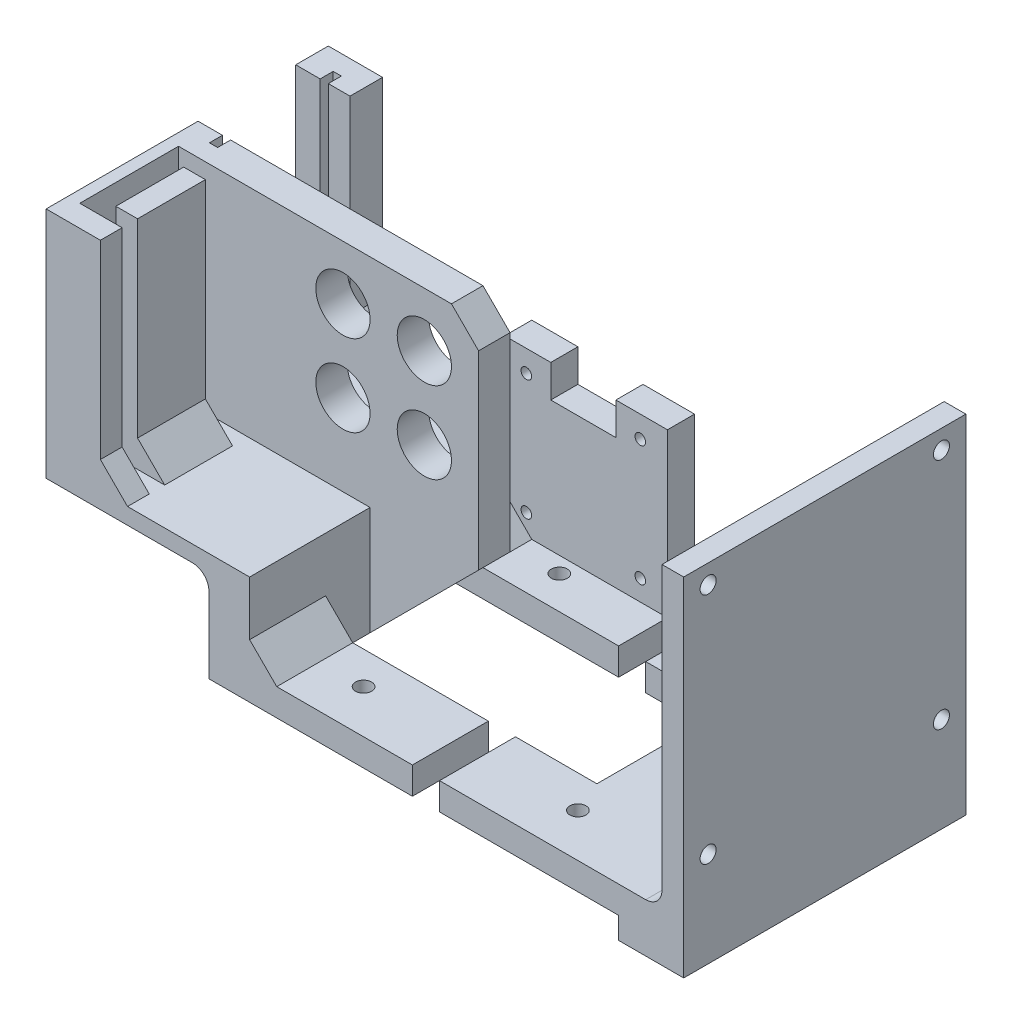
SolidWorks part; units mm, degrees
note: The reader was unsure of these and kept them because the rebuilt part matched: shared geometry of "草图12<4>".
ref_plane "前视基准面" through (0, 0, 0) normal (0, 0, 1) x (1, 0, 0)
ref_plane "上视基准面" through (0, 0, 0) normal (0, 1, 0) x (1, 0, 0)
ref_plane "右视基准面" through (0, 0, 0) normal (1, 0, 0) x (0, 0, -1)
sketch "草图1" plane through (0, 0, 0) normal (0, 1, 0) x (1, 0, 0)
  line L1 (-43.75, 31) -> (43.75, 31)
  line L2 (-43.75, 31) -> (-43.75, -31)
  line L3 (-43.75, -31) -> (43.75, -31)
  line L4 (43.75, 31) -> (43.75, -31)
  line L5 (-43.75, 31) -> (43.75, -31) construction
  line L6 (-43.75, -31) -> (43.75, 31) construction
  point P0 (0, 0)
  dimension "D1" = 62
  dimension "D2" = 87.5
extrude "凸台-拉伸1" add sketch "草图1" along normal blind 60
sketch "草图2" plane through (0, 0, 0) normal (0, -1, 0) x (1, 0, 0)
  line L0 (43.75, -31) -> (-43.75, -31) construction
  line L1 (43.75, 31) -> (31.75, 31)
  line L2 (43.75, 31) -> (43.75, -31)
  line L3 (43.75, -31) -> (31.75, -31)
  line L4 (31.75, 31) -> (31.75, -31)
  dimension "D1" = 12
extrude "凸台-拉伸2" add sketch "草图2" along normal blind 4
sketch "草图4" plane through (0, 0, 0) normal (0, -1, 0) x (1, 0, 0)
  line L0 (0, 0) -> (43.75, 0) construction
  line L1 (43.75, -31) -> (43.75, 31) construction
  line L2 (31.75, 31) -> (31.75, -31) construction
  line L3 (19.75, 6) -> (29.75, 6)
  line L4 (19.75, 6) -> (19.75, -6)
  line L5 (19.75, -6) -> (29.75, -6)
  line L6 (29.75, 6) -> (29.75, -6)
  line L7 (19.75, 6) -> (29.75, -6) construction
  line L8 (19.75, -6) -> (29.75, 6) construction
  line L9 (0, 0) -> (-43.75, 0) construction
  line L10 (-43.75, -31) -> (-43.75, 31) construction
  line L12 (-36.25, 12) -> (13.75, 12)
  line L13 (-36.25, 12) -> (-36.25, -12)
  line L14 (-36.25, -12) -> (13.75, -12)
  line L15 (13.75, 12) -> (13.75, -12)
  line L16 (-36.25, 12) -> (13.75, -12) construction
  line L17 (-36.25, -12) -> (13.75, 12) construction
  circle A0 centre (16.25, -18) radius 1.48 construction
  circle A3 centre (16.25, -18) radius 1.48
  circle A4 centre (-23.25, 18) radius 1.48 construction
  circle A5 centre (-23.25, -18.0759) radius 1.48 construction
  circle A6 centre (-23.25, -18.0759) radius 1.48
  circle A7 centre (-23.25, 18) radius 1.48
  circle A8 centre (16.25, 18) radius 1.48 construction
  circle A9 centre (16.25, 18) radius 1.48
  point P17 (24.75, 0)
  point P27 (-11.25, 0)
  dimension "D1" = 2
  dimension "D2" = 10
  dimension "D3" = 12
  dimension "D4" = 24
  dimension "D5" = 50
  dimension "D6" = 6
extrude "切除-拉伸2" cut sketch "草图4" against normal blind 10
sketch "草图6" plane through (0, 60, 0) normal (0, 1, 0) x (1, 0, 0)
  line L0 (-43.75, 31) -> (-43.75, -31) construction
  line L1 (43.75, -31) -> (-43.75, -31)
  line L2 (43.75, -31) -> (43.75, -26)
  line L3 (43.75, -26) -> (-43.75, -26)
  line L4 (-43.75, -31) -> (-43.75, -26)
  line L5 (40.679, 0) -> (-87.179, 0) construction
  line L6 (43.75, 26) -> (-43.75, 26)
  line L7 (-43.75, 31) -> (-43.75, 26)
  line L8 (43.75, 31) -> (-43.75, 31)
  line L9 (43.75, 31) -> (43.75, 26)
  dimension "D1" = 5
extrude "切除-拉伸3" cut sketch "草图6" against normal blind 100
sketch "草图7" plane through (-43.75, 0, 0) normal (-1, 0, 0) x (0, 0, 1)
  line L0 (26, 0) -> (26, 60) construction
  line L1 (-26, 60) -> (26, 60)
  line L2 (-26, 60) -> (-26, 17)
  line L3 (-26, 17) -> (26, 17)
  line L4 (26, 60) -> (26, 17)
  dimension "D1" = 43
extrude "凸台-拉伸3" add sketch "草图7" along normal blind 30
sketch "草图9" plane through (0, 60, 0) normal (0, 1, 0) x (1, 0, 0)
  line L0 (0, 0) -> (-63.75, 0) construction
  line L1 (39.75, -26) -> (-63.75, -26)
  line L2 (39.75, -26) -> (39.75, 26)
  line L3 (39.75, 26) -> (-63.75, 26)
  line L4 (-73.75, -26) -> (43.75, -26)
  line L5 (43.75, -26) -> (43.75, 26)
  line L6 (43.75, 26) -> (-73.75, 26)
  line L7 (-73.75, 26) -> (-73.75, -26)
  line L8 (-73.75, -26) -> (43.75, -26)
  line L9 (43.75, -26) -> (43.75, 26)
  line L10 (43.75, 26) -> (-73.75, 26)
  line L11 (-73.75, 26) -> (-73.75, -26)
  line L12 (-63.75, -26) -> (-63.75, 26)
  dimension "D2" = 4
  dimension "D3" = 10
  dimension "D1" = 0
extrude "切除-拉伸4" cut sketch "草图9" against normal blind 40 contours L2 L1 L12 L3
sketch "草图10" plane through (0, 20, 0) normal (0, 1, 0) x (1, 0, 0)
  line L1 (39.75, -26) -> (-36.25, -26)
  line L2 (39.75, -26) -> (39.75, 26)
  line L3 (39.75, 26) -> (-36.25, 26)
  line L4 (39.75, 26) -> (-63.75, 26)
  line L5 (-63.75, 26) -> (-63.75, -26)
  line L6 (-63.75, -26) -> (39.75, -26)
  line L7 (39.75, -26) -> (39.75, 26)
  line L8 (39.75, 26) -> (-63.75, 26)
  line L9 (-63.75, 26) -> (-63.75, -26)
  line L10 (-63.75, -26) -> (39.75, -26)
  line L11 (39.75, -26) -> (39.75, 26)
  line L12 (-36.25, -26) -> (-36.25, 26)
  line M7 (39.75, 26) -> (-63.75, 26)
  line M9 (-63.75, -26) -> (39.75, -26)
  line M10 (39.75, -26) -> (39.75, 26)
  dimension "D2" = 76
  dimension "D1" = 0
extrude "切除-拉伸5" cut sketch "草图10" against normal blind 15 contours L12 M9 M10 M7
sketch "草图11" plane through (43.75, 0, 0) normal (1, 0, 0) x (0, 0, -1)
  line L0 (0, 0) -> (0, 60) construction
  line L1 (-26, 60) -> (26, 60) construction
  line L3 (-21.5, 56.5) -> (21.5, 56.5) construction
  line L4 (-21.5, 56.5) -> (-21.5, 13.5) construction
  line L5 (-21.5, 13.5) -> (21.5, 13.5) construction
  line L6 (21.5, 56.5) -> (21.5, 13.5) construction
  line L7 (-21.5, 56.5) -> (21.5, 13.5) construction
  line L8 (-21.5, 13.5) -> (21.5, 56.5) construction
  circle A0 centre (-21.5, 56.5) radius 1.48
  circle A1 centre (21.5, 56.5) radius 1.48
  circle A2 centre (-21.5, 13.5) radius 1.48
  circle A3 centre (21.5, 13.5) radius 1.48
  point P5 (0, 35)
  dimension "D1" = 43
  dimension "D2" = 43
  dimension "D3" = 25
extrude "切除-拉伸6" cut sketch "草图11" against normal blind 10
sketch "草图12" plane through (0, 60, 0) normal (0, 1, 0) x (1, 0, 0)
  line L0 (-63.75, -26) -> (-63.75, 26) construction
  line L1 (-63.75, -19.15) -> (-67.75, -19.15)
  line L2 (-63.75, -19.15) -> (-63.75, -6.65)
  line L3 (-63.75, -6.65) -> (-67.75, -6.65)
  line L4 (-67.75, -19.15) -> (-67.75, -6.65)
  line L5 (-63.75, -26) -> (-73.75, -26) construction
  line L6 (-63.75, -3.8) -> (-71.55, -3.8)
  line L7 (-63.75, -3.8) -> (-63.75, -22)
  line L8 (-63.75, -22) -> (-71.55, -22)
  line L9 (-71.55, -3.8) -> (-71.55, -22)
  line L10 (-73.75, 26) -> (-63.75, 26) construction
  line L11 (-63.75, 20) -> (-67.75, 20)
  line L12 (-63.75, 20) -> (-63.75, 2)
  line L13 (-63.75, 2) -> (-67.75, 2)
  line L14 (-67.75, 20) -> (-67.75, 2)
  line L15 (-73.75, -26) -> (-73.75, 26) construction
  line L16 (-67.75, 22.4) -> (-69.25, 22.4)
  line L17 (-67.75, 22.4) -> (-67.75, -0.4)
  line L18 (-67.75, -0.4) -> (-69.25, -0.4)
  line L19 (-69.25, 22.4) -> (-69.25, -0.4)
  line L20 (-69.25, 20) -> (-73.75, 20)
  line L21 (-69.25, 20) -> (-69.25, 2)
  line L22 (-69.25, 2) -> (-73.75, 2)
  line L23 (-73.75, 20) -> (-73.75, 2)
  line M6 (-63.75, -26) -> (-63.75, 26)
  line M8 (-73.75, 26) -> (-73.75, -26)
  dimension "D1" = 12.5
  dimension "D2" = 4
  dimension "D3" = 18.2
  dimension "D4" = 2.85
  dimension "D5" = 4
  dimension "D6" = 3.8
  dimension "D7" = 4
  dimension "D8" = 18
  dimension "D9" = 6
  dimension "D10" = 1.5
  dimension "D11" = 22.8
  dimension "D12" = 2.4
extrude "切除-拉伸7" cut sketch "草图12" against normal blind 40 contours L6 L9 L8 L1 L4 L3 M6
extrude "切除-拉伸8" cut sketch "草图12<4>" against normal blind 40 contours L16 L19 L18 L17 L14 | L11 L14 L13 M6 | L22 L19 L20 M8
sketch "草图12<4>" plane through (0, 60, 0) normal (0, 1, 0) x (1, 0, 0) same geometry as "草图12"
sketch "草图13" plane through (0, 20, 0) normal (0, 1, 0) x (1, 0, 0)
  line L0 (-36.25, -26) -> (-36.25, 26) construction
  line L1 (-63.75, 2) -> (-36.25, 2)
  line L2 (-63.75, 2) -> (-63.75, -3.8)
  line L3 (-63.75, -3.8) -> (-36.25, -3.8)
  line L4 (-36.25, 2) -> (-36.25, -3.8)
extrude "凸台-拉伸4" add sketch "草图13" along normal blind 40
sketch "草图14" plane through (0, 5, 0) normal (0, 1, 0) x (1, 0, 0)
  line L1 (-36.25, 26) -> (-6.25, 26)
  line L2 (-36.25, 26) -> (-36.25, 21)
  line L3 (-36.25, 21) -> (-6.25, 21)
  line L4 (-6.25, 26) -> (-6.25, 21)
  dimension "D1" = 30
  dimension "5" = 5
extrude "凸台-拉伸5" add sketch "草图14" along normal blind 30
sketch "草图15" plane through (0, 0, -26) normal (0, 0, -1) x (-1, 0, 0)
  line L0 (6.25, 35) -> (36.25, 35) construction
  line L1 (11.25, 31) -> (32.25, 31) construction
  line L2 (11.25, 31) -> (11.25, 8.8) construction
  line L3 (11.25, 8.8) -> (32.25, 8.8) construction
  line L4 (32.25, 31) -> (32.25, 8.8) construction
  line L5 (6.25, 35) -> (6.25, 5) construction
  line L6 (21.75, 31) -> (21.75, 8.8) construction
  line L7 (21.75, 31) -> (21.75, 35) construction
  line L9 (15.75, 35) -> (27.75, 35)
  line L10 (15.75, 35) -> (15.75, 29)
  line L11 (15.75, 29) -> (27.75, 29)
  line L12 (27.75, 35) -> (27.75, 29)
  circle A0 centre (11.25, 31) radius 0.98
  circle A1 centre (32.25, 31) radius 0.98
  circle A2 centre (11.25, 8.8) radius 0.98
  circle A3 centre (32.25, 8.8) radius 0.98
  dimension "D5" = 12
  dimension "D1" = 21
  dimension "D2" = 22.2
  dimension "D3" = 4
  dimension "D4" = 5
  dimension "D6" = 6
  dimension "D7" = 6
extrude "切除-拉伸9" cut sketch "草图15" against normal blind 10
fillet "圆角2" radius 3 1 edges at (-43.75, 17, 0)
sketch "草图16" plane through (0, 5, 0) normal (0, 1, 0) x (1, 0, 0)
  line L0 (0, 0) -> (39.75, 0) construction
  line L1 (39.75, -26) -> (39.75, 26) construction
  line L2 (-36.25, -26) -> (39.75, -26) construction
  line L3 (-1.25, -26) -> (-6.25, -26)
  line L4 (-1.25, -26) -> (-1.25, -12)
  line L5 (-1.25, -12) -> (-6.25, -12)
  line L6 (-6.25, -26) -> (-6.25, -12)
  line L7 (13.75, -12) -> (-36.25, -12) construction
  line L8 (-1.25, 12) -> (-6.25, 12)
  line L9 (-6.25, 26) -> (-6.25, 12)
  line L10 (-1.25, 26) -> (-6.25, 26)
  line L11 (-1.25, 26) -> (-1.25, 12)
  line L12 (13.75, 12) -> (13.75, -12) construction
  dimension "D1" = 5
  dimension "D2" = 15
extrude "切除-拉伸10" cut sketch "草图16" against normal blind 10
chamfer "倒角4" distance 5 angle 45 4 edges at (-63.75, 20, -23) (-36.25, 5, 19) (-36.25, 5, -16.5) (-36.25, 20, -23.5)
sketch "草图17" plane through (-36.25, 0, 0) normal (1, 0, 0) x (0, 0, -1)
  line L1 (-3.8, 60) -> (2, 60)
  line L2 (-3.8, 60) -> (-3.8, 20)
  line L3 (-3.8, 20) -> (2, 20)
  line L4 (2, 60) -> (2, 20)
  line L12 (2, 20) -> (2, 60)
  line L13 (2, 60) -> (-3.8, 60)
  line L14 (-3.8, 60) -> (-3.8, 20)
  line L15 (-3.8, 20) -> (-26, 20)
  line L16 (-26, 20) -> (-26, 10)
  line L17 (-26, 10) -> (-12, 10)
  line L18 (-12, 10) -> (-12, 0)
  line L19 (-12, 0) -> (12, 0)
  line L20 (12, 0) -> (12, 10)
  line L21 (12, 10) -> (21, 10)
  line L22 (21, 10) -> (21, 20)
  line L23 (21, 20) -> (2, 20)
  line L24 (2, 20) -> (2, 60)
  line L26 (-3.8, 60) -> (-3.8, 20)
  line L27 (-3.8, 20) -> (-26, 20)
  line L28 (-26, 20) -> (-26, 10)
  line L29 (-26, 10) -> (-12, 10)
  line L30 (-12, 10) -> (-12, 0)
  line L31 (-12, 0) -> (12, 0)
  line L32 (12, 0) -> (12, 10)
  line L33 (12, 10) -> (21, 10)
  line L34 (21, 10) -> (21, 20)
  line L35 (21, 20) -> (2, 20)
  line L40 (2, 60) -> (-3.8, 60)
  dimension "D1" = 0
extrude "凸台-拉伸6" add sketch "草图17" along normal blind 20
chamfer "倒角5" distance 20 angle 45 1 edges at (-36.25, 20, 0.9)
chamfer "倒角6" distance 5 angle 45 1 edges at (-16.25, 60, 0.9)
sketch "草图18" plane through (0, 0, -2) normal (0, 0, -1) x (-1, 0, 0)
  line L0 (16.25, 50) -> (63.75, 50) construction
  line L1 (16.25, 20) -> (16.25, 55) construction
  line L2 (63.75, 25) -> (63.75, 60) construction
  line L3 (21.25, 60) -> (67.75, 60) construction
  line L4 (16.25, 35) -> (63.75, 35) construction
  circle A0 centre (26.25, 50) radius 5
  circle A1 centre (41.25, 50) radius 5
  circle A2 centre (26.25, 35) radius 5
  circle A3 centre (41.25, 35) radius 5
  dimension "D2" = 10
  dimension "D3" = 10
  dimension "D7" = 10
  dimension "D8" = 10
  dimension "D1" = 10
  dimension "D4" = 10
  dimension "D5" = 15
  dimension "D6" = 15
extrude "切除-拉伸11" cut sketch "草图18" against normal blind 20
fillet "圆角3" radius 3 1 edges at (39.75, 5, 0)
